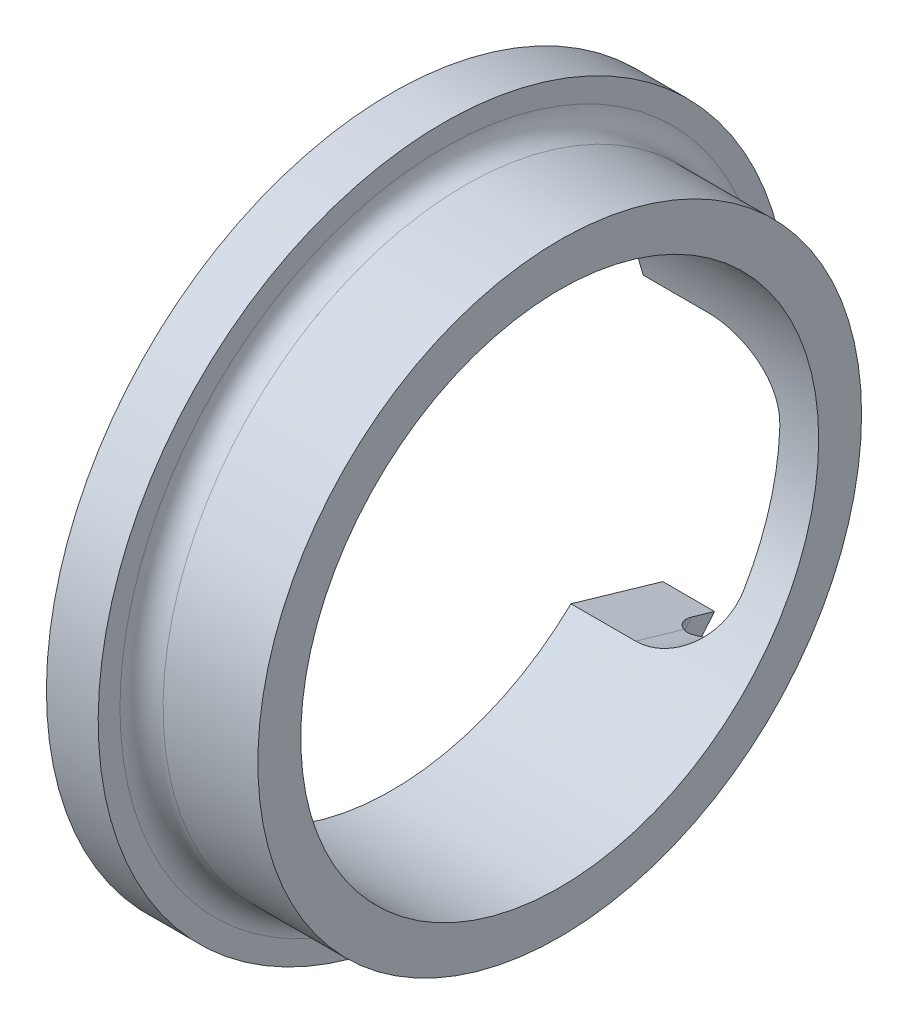
SolidWorks part; units mm, degrees
material "6061-T6 (SS)"
ref_plane "Front Plane" through (0, 0, 0) normal (0, 0, 1) x (1, 0, 0)
ref_plane "Top Plane" through (0, 0, 0) normal (0, 1, 0) x (1, 0, 0)
ref_plane "Right Plane" through (0, 0, 0) normal (1, 0, 0) x (0, 0, -1)
sketch "Sketch1" plane through (0, 0, 0) normal (0, 0, 1) x (1, 0, 0)
  line L0 (-37.8541, 8.89) -> (-37.8541, 10.167)
  line L1 (-37.8541, 8.89) -> (-34.4281, 8.89)
  line L2 (-39.3781, 10.167) -> (-39.3781, 7.627)
  line L3 (-39.3781, 7.627) -> (-34.4281, 7.627)
  line L4 (-34.4281, 8.89) -> (-34.4281, 7.627)
  line L5 (-37.8541, 10.167) -> (-39.3781, 10.167)
  line L7 (0, 0) -> (-47.1489, 0) construction
  line L8 (-39.3781, 10.4991) -> (-39.3781, 46.2794) construction
  line L9 (-34.4281, 15.2446) -> (-34.4281, -15.2446) construction
  dimension "D4" = 17.78
  dimension "D1" = 15.254
  dimension "D2" = 1.524
  dimension "D3" = 2.54
revolve "Revolve1" add sketch "Sketch1" angle 360 about L7
fillet "Fillet1" radius 0.635 1 edges at (-37.8541, 0, -8.89)
ref_plane "Plane1" through (0, -1.7465, -6.0042) normal (0, -0.2793, -0.9602) x (-1, 0, 0)
sketch "Sketch3" plane through (0, -1.7465, -6.0042) normal (0, -0.2793, -0.9602) x (-1, 0, 0)
  line L0 (39.3781, 3.81) -> (39.3781, -3.81)
  line L1 (39.3781, -7.627) -> (39.3781, 7.627) construction
  line L2 (39.3781, -3.81) -> (37.4731, -3.81)
  line L3 (35.5681, -1.905) -> (35.5681, 1.905)
  line L4 (37.4731, 3.81) -> (39.3781, 3.81)
  line L5 (39.3781, -8.89) -> (39.3781, 8.89) construction
  line L6 (39.3781, -8.89) -> (39.3781, 8.89) construction
  line L7 (35.5681, 0) -> (39.3781, 0) construction
  arc A2 (37.4731, -3.81) -> (35.5681, -1.905) centre (37.4731, -1.905) cw
  arc A3 (35.5681, 1.905) -> (37.4731, 3.81) centre (37.4731, 1.905) cw
  dimension "D1" = 7.62
  dimension "D2" = 3.81
extrude "Cut-Extrude1" cut sketch "Sketch3" along normal up to next
equation "\"D1@Sketch1\"=15mm+0.01in"
